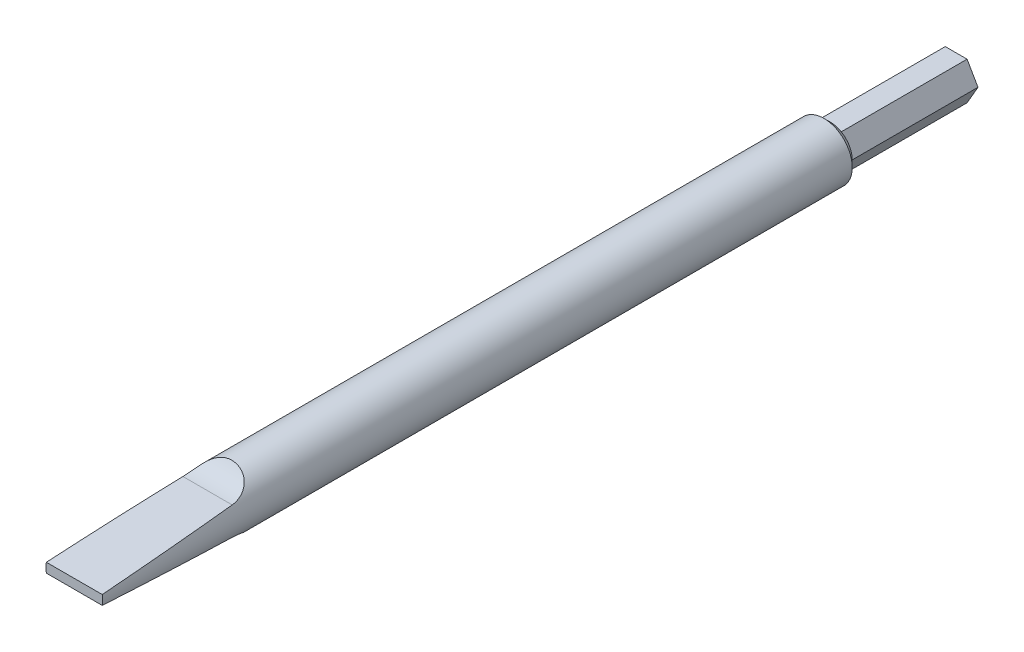
SolidWorks part; units mm, degrees
ref_plane "Front Plane" through (0, 0, 0) normal (0, 0, 1) x (1, 0, 0)
ref_plane "Top Plane" through (0, 0, 0) normal (0, 1, 0) x (1, 0, 0)
ref_plane "Right Plane" through (0, 0, 0) normal (1, 0, 0) x (0, 0, -1)
sketch "Sketch1" plane through (0, 0, 0) normal (0, 0, 1) x (1, 0, 0)
  line L1 (1.7321, 3) -> (-1.7321, 3)
  line L2 (-1.7321, 3) -> (-3.4641, 0)
  line L3 (-3.4641, 0) -> (-1.7321, -3)
  line L4 (-1.7321, -3) -> (1.7321, -3)
  line L5 (1.7321, -3) -> (3.4641, 0)
  line L6 (3.4641, 0) -> (1.7321, 3)
  circle A0 centre (0, 0) radius 4.5
  point P1 (0, 3)
  dimension "D2" = 9
  dimension "D1" = 6
extrude "Boss-Extrude1" add sketch "Sketch1" against normal blind 20 contours L5 L6 L1 L2 L3 L4 region at (0, 0, 0)
extrude "Boss-Extrude2" add sketch "Sketch1<3>" along normal blind 120 contours A0 L6 L5 L4 L3 L2 L1 | L5 L6 L1 L2 L3 L4 region at (0, 0, 0) region at (-4.3727, 0, 0)
sketch "Sketch1<3>" plane through (0, 0, 0) normal (0, 0, 1) x (1, 0, 0) same geometry as "Sketch1"
chamfer "Chamfer1" distance 1 angle 45 1 edges at (4.5, 0, 0)
sketch "Sketch2" plane through (0, 0, 0) normal (1, 0, 0) x (0, 0, -1)
  line L0 (-120, -0.75) -> (-120, 0.75)
  line L1 (-120, 4.5) -> (-120, -4.5) construction
  line L2 (-120, -0.75) -> (-120, -4.5)
  line L3 (-1, 4.5) -> (-120, 4.5) construction
  line L4 (-120, -4.5) -> (-95, -4.5)
  line L5 (-120, -4.5) -> (-1, -4.5) construction
  line L6 (-120.0007, 0) -> (-114.0497, 0) construction
  line L7 (-120, 0.75) -> (-98.8487, 2.229)
  line L8 (-120, -0.75) -> (-98.8487, -2.229)
  line L9 (-120, 0.75) -> (-120, 4.5)
  line L10 (-120, 4.5) -> (-95, 4.5)
  line L11 (-120, 0.75) -> (-114.3003, 0.75) construction
  arc A0 (-95, 4.5) -> (-98.8487, 2.229) centre (-99.1975, 7.2169) cw
  arc A1 (-95, -4.5) -> (-98.8487, -2.229) centre (-99.1975, -7.2169) ccw
  point P5 (-120, 0)
  point P7 (-95, 4.5)
  point P8 (-95, -4.5)
  dimension "D4" = 4
  dimension "D5" = 5
  dimension "D1" = 1.5
  dimension "D2" = 4.5
  dimension "D3" = 25
extrude "Cut-Extrude3" cut sketch "Sketch2" against normal blind 120 and the other way blind 120 contours L2 L4 A1 L8 | L9 L10 A0 L7
